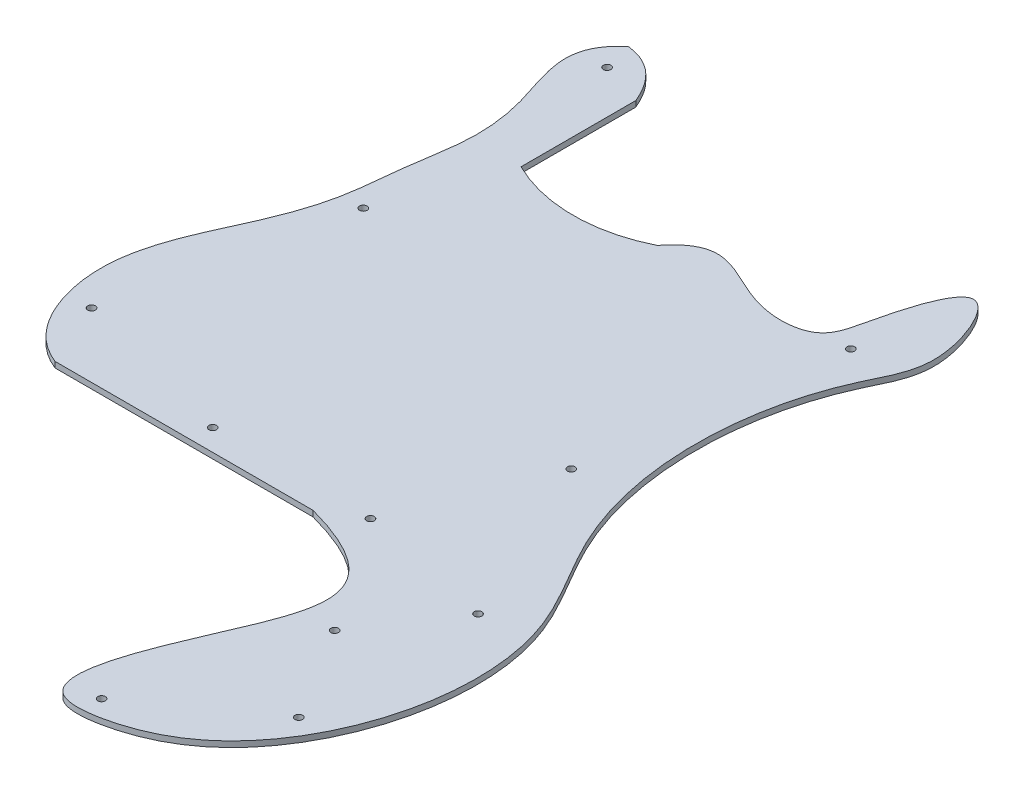
SolidWorks part; units mm, degrees
ref_plane "Front Plane" through (0, 0, 0) normal (0, 0, 1) x (1, 0, 0)
ref_plane "Top Plane" through (0, 0, 0) normal (0, 1, 0) x (1, 0, 0)
ref_plane "Right Plane" through (0, 0, 0) normal (1, 0, 0) x (0, 0, -1)
sketch "Sketch1" plane through (0, 0, 0) normal (0, 1, 0) x (1, 0, 0)
  line L0 (0, 0) -> (114.3, 0)
  line L1 (88.9, 0) -> (88.9, 254) construction
  line L2 (28.575, 228.6) -> (28.575, 177.8)
  line L3 (58.7375, 238.2047) -> (58.7375, 170.688) construction
  line L4 (88.9, 177.8) -> (88.9, 186.182)
  arc A0 (28.575, 177.8) -> (88.9, 177.8) centre (58.7375, 238.2047) ccw
  circle A1 centre (60.325, 9.525) radius 1.6764
  circle A2 centre (130.175, 9.525) radius 1.6764
  circle A3 centre (-12.3825, 28.575) radius 1.6764
  circle A4 centre (9.525, 127) radius 1.6764
  circle A5 centre (9.525, 234.95) radius 1.6764
  circle A6 centre (173.0375, 234.95) radius 1.6764
  circle A7 centre (171.45, 180.975) radius 1.6764
  circle A8 centre (155.575, 73.025) radius 1.6764
  circle A9 centre (190.5, -3.175) radius 1.6764
  circle A10 centre (190.5, -82.55) radius 1.6764
  circle A11 centre (139.7, -119.0625) radius 1.6764
  circle A12 centre (165.1, -41.275) radius 1.6764
  spline S0 degree 3 poles (0, 0) (-11.53, 4.5145) (-23.5981, 21.7649) (-27.1419, 51.1961) (-19.6131, 77.0698) (-7.4978, 100.9452) (1.0987, 126.4824) (2.5386, 152.4514) (7.7782, 177.7738) (3.4996, 210.5141) (-10.048, 234.3249) (6.35, 247.65) knots 0 0 0 0 0.130339 0.226964 0.325793 0.430447 0.530898 0.627523 0.724148 0.820773 1 1 1 1
  spline S1 degree 2 poles (6.35, 247.65) (21.4241, 246.03) (28.575, 228.6) knots 0 0 0 1 1 1
  spline S2 degree 3 poles (114.3, 0) (170.6231, -15.3245) (142.7787, -51.0149) (117.0722, -130.8653) (166.9109, -124.7474) (211.2624, -85.6459) (223.292, -5.854) (185.7671, 45.1016) (169.1709, 100.6222) (175.8692, 155.1375) (199.7965, 194.9971) (178.5502, 245.0523) (165.6085, 201.3621) (161.1325, 176.1365) (122.4048, 174.7436) (104.819, 197.9947) (88.9, 177.8) knots 0 0 0 0 0.152581 0.216738 0.247448 0.331739 0.475087 0.544037 0.604471 0.727585 0.765192 0.816611 0.866125 0.890624 0.926825 1 1 1 1
  point P6 (88.9, 12.7)
  point P8 (88.9, 25.4)
  point P10 (88.9, 50.8)
  point P12 (88.9, 76.2)
  point P13 (88.9, 177.8)
  point P15 (88.9, 177.8)
  point P16 (88.9, 101.6)
  point P17 (88.9, 127)
  point P18 (88.9, 152.4)
  point P19 (88.9, 247.65)
  point P20 (88.9, 203.2)
  point P40 (88.9, 228.6)
  point P59 (108.0008, 187.7256)
  point P61 (134.6404, 177.8)
  dimension "D27" = 3.3528
  dimension "D39" = 50.8
  dimension "D40" = 119.0625
  dimension "D41" = 101.6
  dimension "D42" = 82.55
  dimension "D47" = 180.975
  dimension "D48" = 82.55
  dimension "D49" = 84.1375
  dimension "D1" = 114.3
  dimension "D2" = 25.4
  dimension "D3" = 12.7
  dimension "D4" = 25.4
  dimension "D5" = 50.8
  dimension "D6" = 76.2
  dimension "D8" = 25.4
  dimension "D9" = 25.4
  dimension "D10" = 254
  dimension "D11" = 25.4
  dimension "D12" = 104.775
  dimension "D13" = 111.125
  dimension "D14" = 114.3
  dimension "D15" = 107.95
  dimension "D16" = 96.8375
  dimension "D17" = 88.9
  dimension "D18" = 85.725
  dimension "D19" = 82.55
  dimension "D20" = 85.725
  dimension "D21" = 92.075
  dimension "D22" = 247.65
  dimension "D23" = 82.55
  dimension "D24" = 60.325
  dimension "D25" = 7.112
  dimension "D26" = 8.382
  dimension "D28" = 79.375
  dimension "D29" = 234.95
  dimension "D30" = 79.375
  dimension "D31" = 127
  dimension "D32" = 28.575
  dimension "D33" = 101.2825
  dimension "D34" = 28.575
  dimension "D35" = 9.525
  dimension "D36" = 69.85
  dimension "D37" = 41.275
  dimension "D38" = 76.2
  dimension "D43" = 101.6
  dimension "D44" = 3.175
  dimension "D45" = 66.675
  dimension "D46" = 73.025
  dimension "D7" = 6
extrude "Boss-Extrude1" add sketch "Sketch1" along normal blind 2.54 contours L0 S2 A0 L2 S1 S0 A1 A2 A3 A4 A5 A7 A8 A9 A10 A11 A12 region at (101.7422, 0, -67.1195)
